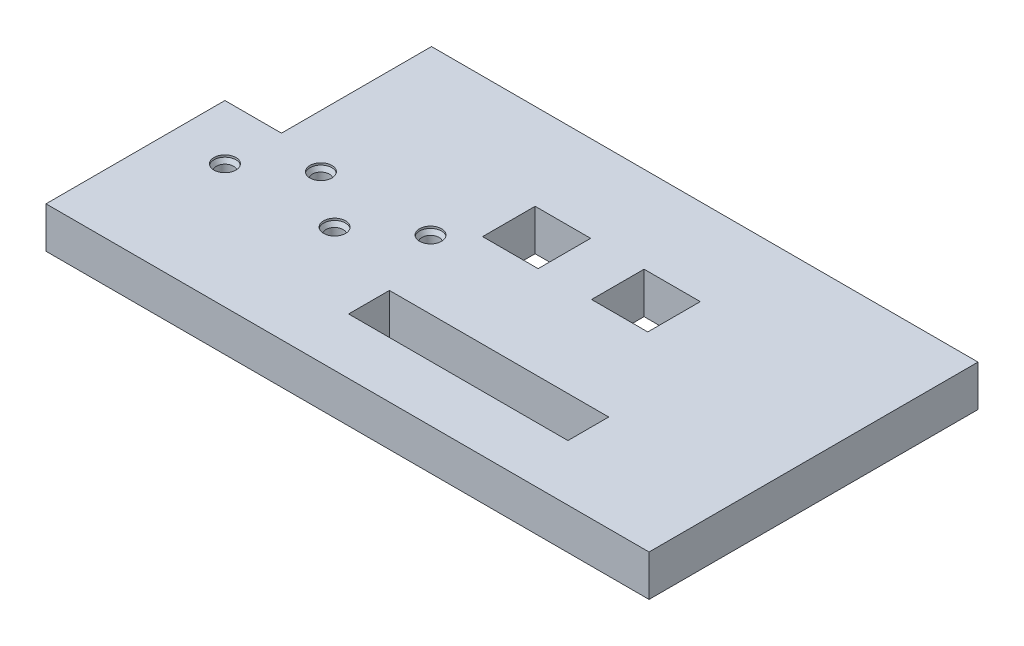
SolidWorks part; units mm, degrees
material "Plain Carbon Steel"
ref_plane "Front Plane" through (0, 0, 0) normal (0, 0, 1) x (1, 0, 0)
ref_plane "Top Plane" through (0, 0, 0) normal (0, 1, 0) x (1, 0, 0)
ref_plane "Right Plane" through (0, 0, 0) normal (1, 0, 0) x (0, 0, -1)
sketch "Sketch1" plane through (0, 0, 0) normal (0, 1, 0) x (1, 0, 0)
  line L1 (-110, -60) -> (110, -60)
  line L2 (-110, -60) -> (-110, 60)
  line L3 (-110, 60) -> (110, 60)
  line L4 (110, -60) -> (110, 60)
  line L5 (-110, -60) -> (110, 60) construction
  line L6 (-110, 60) -> (110, -60) construction
  point P0 (0, 0)
  dimension "D1" = 120
  dimension "D2" = 220
extrude "Boss-Extrude1" add sketch "Sketch1" against normal blind 15
sketch "Sketch2" plane through (0, 0, 0) normal (0, 1, 0) x (1, 0, 0)
  line L1 (-110, 60) -> (-89.3675, 60)
  line L2 (-110, 60) -> (-110, 5.27)
  line L3 (-110, 5.27) -> (-89.3675, 5.27)
  line L4 (-89.3675, 60) -> (-89.3675, 5.27)
  line L5 (-90, -14.72) -> (-89.3675, 5.27) construction
  line L10 (-70, 0.28) -> (-89.3675, 5.27) construction
  circle A0 centre (-70, 0.28) radius 3.1 construction
  circle A1 centre (-90, -14.72) radius 3.1 construction
  point P7 (0, 0)
  point P10 (0, 0)
  dimension "D1" = 20
extrude "Cut-Extrude1" cut sketch "Sketch2" against normal up to next
sketch "Sketch3" plane through (0, 0, 0) normal (0, 1, 0) x (1, 0, 0)
  line L0 (-20, 27.5) -> (-20, 9.28) construction
  line L1 (-20, 9.28) -> (0.25, 9.28) construction
  line L2 (0.25, 9.28) -> (0.25, 27.5) construction
  line L3 (19.75, 27.5) -> (19.75, 9.28) construction
  line L4 (19.75, 9.28) -> (40.25, 9.28) construction
  line L5 (40.25, 9.28) -> (40.25, 27.5) construction
  line L6 (-20, 28.44) -> (-20, 9.28)
  line L7 (-20, 9.28) -> (0.25, 9.28)
  line L8 (0.25, 9.28) -> (0.25, 28.44)
  line L9 (19.75, 28.44) -> (19.75, 9.28)
  line L10 (19.75, 9.28) -> (40.25, 9.28)
  line L11 (40.25, 9.28) -> (40.25, 28.44)
  line L12 (-20, 28.44) -> (0.25, 28.44)
  line L14 (19.75, 28.44) -> (40.25, 28.44)
  line L15 (0.31, 28.5) -> (-20.06, 28.5) construction
  dimension "D1" = 0.06
extrude "Cut-Extrude2" cut sketch "Sketch3" against normal up to next
sketch "Sketch4" plane through (0, 0, 0) normal (0, 1, 0) x (1, 0, 0)
  line L0 (-20.06, -39.66) -> (60.06, -39.66) construction
  line L1 (60, -24.72) -> (-20, -24.72)
  line L2 (60, -24.72) -> (60, -39.6)
  line L3 (60, -39.6) -> (-20, -39.6)
  line L4 (-20, -24.72) -> (-20, -39.6)
  dimension "D1" = 80
  dimension "D2" = 0.06
  dimension "D3" = 14.88
extrude "Cut-Extrude3" cut sketch "Sketch4" against normal up to next
hole_wizard "Ø6.2 (6.2) Diameter Hole1" positions "Sketch7" profile "Sketch6" hole size "Ø6.2" standard "ISO" end condition through all
sketch "Sketch7" plane through (0, 0, 0) normal (0, 1, 0) x (1, 0, 0)
  point P0 (-30, 0.28)
  point P3 (-50, -14.72)
  point P6 (-70, 0.28)
  point P9 (-90, -14.72)
sketch "Sketch6" plane through (-30, 0, -0.28) normal (1, 0, 0) x (0, 0, 1)
  line L0 (0, 0) -> (0, 15)
  line L1 (0, 15) -> (3.1, 15)
  line L2 (3.1, 15) -> (3.1, 0)
  line L5 (3.1, 0) -> (0, 0)
  line L11 (0, -6.35) -> (0, 107.95) construction
  dimension "Thru Hole Dia." = 6.2
  dimension "Thru Hole Depth" = 15
sketch "Sketch8" plane through (0, 0, 0) normal (0, 1, 0) x (1, 0, 0)
  circle A0 centre (-90, -14.72) radius 4
  circle A1 centre (-70, 0.28) radius 4
  circle A2 centre (-50, -14.72) radius 4
  circle A3 centre (-30, 0.28) radius 4
  dimension "D1" = 8
extrude "Cut-Extrude4" cut sketch "Sketch8" against normal blind 0.5
chamfer "Chamfer1" distance 1.8 angle 30 4 edges at (-90, -0.5, 17.82) (-30, -0.5, 2.82) (-50, -0.5, 17.82) (-70, -0.5, 2.82) first distance on face at (-90, -15, 17.82) first distance on face at (-30, -15, 2.82) first distance on face at (-50, -15, 17.82) first distance on face at (-70, -15, 2.82)
